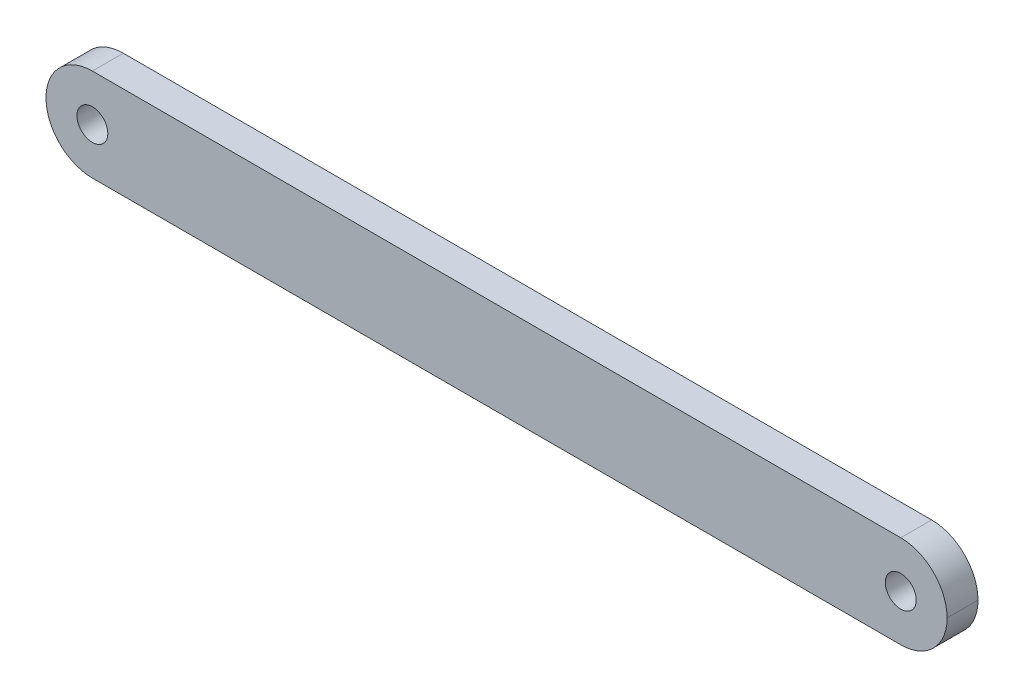
SolidWorks part; units mm, degrees
ref_plane "Front" through (0, 0, 0) normal (0, 0, 1) x (1, 0, 0)
ref_plane "Top" through (0, 0, 0) normal (0, 1, 0) x (1, 0, 0)
ref_plane "Right" through (0, 0, 0) normal (1, 0, 0) x (0, 0, -1)
sketch "Sketch1" plane through (0, 0, 0) normal (0, 0, 1) x (1, 0, 0)
  line L0 (0, 3) -> (58.32, 3) construction
  line L1 (0, 0) -> (58.32, 0)
  line L2 (0, 0) -> (0, 6)
  line L3 (0, 6) -> (58.32, 6)
  line L4 (58.32, 0) -> (58.32, 6)
  circle A0 centre (3, 3) radius 1
  circle A1 centre (55.32, 3) radius 1
  dimension "D1" = 2
  dimension "D2" = 2
  dimension "D3" = 2
  dimension "D4" = 2
  dimension "D5" = 52.32
  dimension "D6" = 6
extrude "Boss-Extrude1" add sketch "Sketch1" along normal blind 2
fillet "Fillet1" radius 3 4 edges at (58.32, 0, 1) (58.32, 6, 1) (0, 0, 1) (0, 6, 1)
